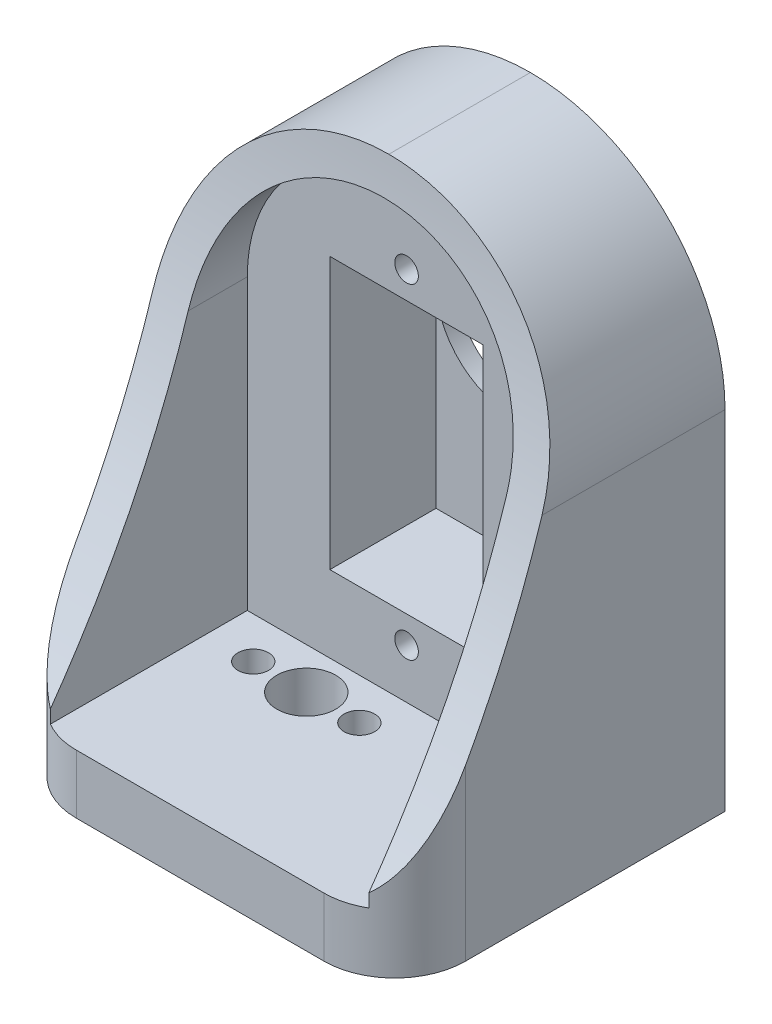
SolidWorks part; units mm, degrees
ref_plane "Front Plane" through (0, 0, 0) normal (0, 0, 1) x (1, 0, 0)
ref_plane "Top Plane" through (0, 0, 0) normal (0, 1, 0) x (1, 0, 0)
ref_plane "Right Plane" through (0, 0, 0) normal (1, 0, 0) x (0, 0, -1)
sketch "Sketch1" plane through (0, 0, 0) normal (0, 1, 0) x (1, 0, 0)
  line L9 (-16.5, 14) -> (16.5, 14)
  line L10 (-16.5, 14) -> (-16.5, -14)
  line L11 (-16.5, -14) -> (16.5, -14)
  line L12 (16.5, 14) -> (16.5, -14)
  line L13 (-16.5, 14) -> (16.5, -14) construction
  line L14 (-16.5, -14) -> (16.5, 14) construction
  point P0 (0, 0)
  dimension "D1" = 33
  dimension "D2" = 28
extrude "Boss-Extrude1" add sketch "Sketch1" along normal blind 46
sketch "Sketch2" plane through (16.5, 0, 0) normal (1, 0, 0) x (0, 0, -1)
  line L0 (-14, 0) -> (14, 0) construction
  line L1 (-14, 46) -> (3.5, 46)
  line L2 (-14, 46) -> (-14, 5)
  line L3 (-14, 5) -> (3.5, 5)
  line L4 (3.5, 46) -> (3.5, 5)
  line L5 (14, 46) -> (14, 0) construction
  dimension "D1" = 5
  dimension "D2" = 10.5
extrude "Cut-Extrude1" cut sketch "Sketch2" against normal blind 46
sketch "Sketch3" plane through (16.5, 0, 0) normal (1, 0, 0) x (0, 0, -1)
  line L0 (3.5, 46) -> (2, 46)
  line L2 (-14, 5) -> (3.5, 5) construction
  line L3 (3.5, 5) -> (3.5, 46) construction
  line L4 (-14, 5) -> (3.5, 5)
  line L5 (3.5, 5) -> (3.5, 46)
  spline S0 degree 2 poles (-14, 5) (-0.6823, 23.1585) (2, 46) knots 0 0 0 1 1 1
  point P5 (-6.2064, 17.822)
  dimension "D1" = 1.5
extrude "Boss-Extrude2" add sketch "Sketch3" against normal blind 3
mirror "Mirror1" about plane through (0, 0, 0) normal (1, 0, 0) of "Boss-Extrude2"
sketch "Sketch4" plane through (13.5, 0, 0) normal (-1, 0, 0) x (0, 0, 1)
  line L0 (-3.5, 43) -> (-1.5988, 43)
  line L3 (-3.5, 46) -> (-3.5, 5)
  line L4 (-3.5, 5) -> (14, 5)
  line L5 (-2, 46) -> (-3.5, 46)
  line L6 (-3.5, 46) -> (-3.5, 5)
  line L7 (-3.5, 5) -> (14, 5)
  line L8 (-2, 46) -> (-3.5, 46)
  parabola Q1 (14, 5) -> (-2, 46) focus (42.7722, 37.8071) apex (4.7043, 21.045)
  parabola Q2 (14, 5) -> (-2, 46) focus (42.7722, 37.8071) apex (4.7043, 21.045)
  line M6 (-3.5, 46) -> (-3.5, 5)
  spline M8 degree 2 poles (-2, 46) (0.6823, 23.1585) (14, 5) knots 0 0 0 1 1 1
  line M9 (-2, 46) -> (-3.5, 46)
  dimension "D2" = 3
  dimension "D1" = 0
extrude "Boss-Extrude3" add sketch "Sketch4" along normal up to surface (27 mm away) contours L0 M6 M8 M9 region at (13.5, 44.4407, -2.6498) up to face at (-13.5, 30.625, 1.4375)
fillet "Fillet1" radius 13.5 2 edges
fillet "Fillet2" radius 16.5 2 edges at (16.5, 46, -8) (-16.5, 46, -8)
fillet "Fillet3" radius 6 2 edges at (-16.5, 2.5, 14) (16.5, 2.5, 14)
sketch "Sketch5" plane through (0, 0, -3.5) normal (0, 0, 1) x (1, 0, 0)
  line L0 (-13.5, 5) -> (13.5, 5) construction
  line L1 (-6.5, 34.5) -> (6.5, 34.5)
  line L2 (-6.5, 34.5) -> (-6.5, 11.5)
  line L3 (-6.5, 11.5) -> (6.5, 11.5)
  line L4 (6.5, 34.5) -> (6.5, 11.5)
  line L5 (-6.5, 34.5) -> (6.5, 11.5) construction
  line L6 (-6.5, 11.5) -> (6.5, 34.5) construction
  point P0 (0, 23)
  point P7 (0, 0)
  dimension "D1" = 13
  dimension "D2" = 23
  dimension "D3" = 6.5
extrude "Cut-Extrude4" cut sketch "Sketch5" against normal blind 9
sketch "Sketch6" plane through (0, 0, -12.5) normal (0, 0, 1) x (1, 0, 0)
  line L0 (6.5, 34.5) -> (-6.5, 34.5) construction
  circle A0 centre (0, 28) radius 6.5
  dimension "D1" = 13
  dimension "D2" = 6.5
extrude "Cut-Extrude5" cut sketch "Sketch6" against normal blind 9
sketch "Sketch7" plane through (0, 0, -3.5) normal (0, 0, 1) x (1, 0, 0)
  line L0 (0, 36.8) -> (0, 0) construction
  line L1 (6.5, 34.5) -> (-6.5, 34.5) construction
  circle A0 centre (0, 36.8) radius 1
  circle A1 centre (0, 9.2) radius 1
  dimension "D1" = 2
  dimension "D2" = 2.3
  dimension "D3" = 27.6
extrude "Cut-Extrude6" cut sketch "Sketch7" against normal blind 8
sketch "Sketch8" plane through (0, 5, 0) normal (0, 1, 0) x (1, 0, 0)
  line L0 (-16.5, -1.516) -> (-16.5, -8) construction
  circle A0 centre (-0.5, 0) radius 1.3
  circle A1 centre (-5, 0) radius 2.5
  circle A2 centre (-9.5, 0) radius 1.3
  dimension "D1" = 2.6
  dimension "D2" = 5
  dimension "D3" = 4.5
  dimension "D4" = 9
  dimension "D5" = 11.5
extrude "Cut-Extrude7" cut sketch "Sketch8" against normal through all
